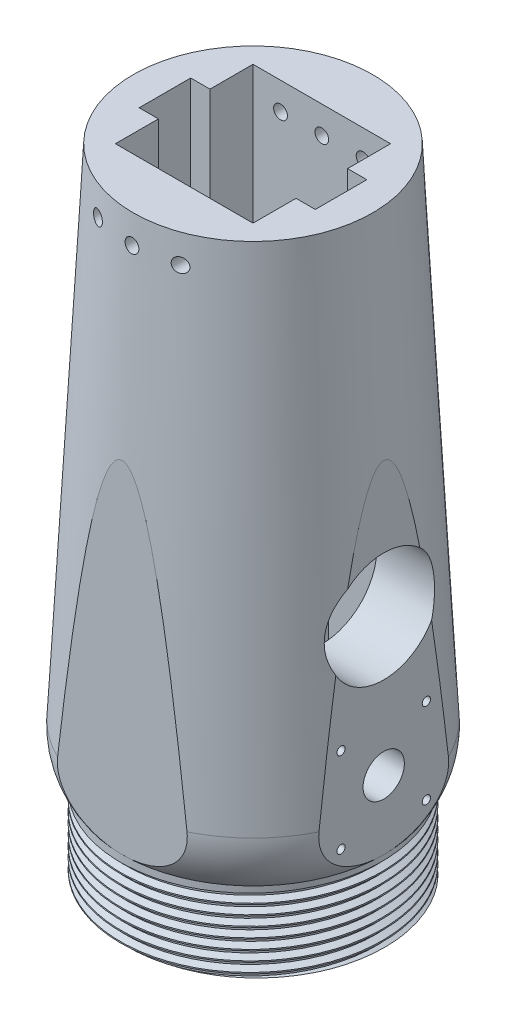
SolidWorks part; units mm, degrees
ref_plane "Front Plane" through (0, 0, 0) normal (0, 0, 1) x (1, 0, 0)
ref_plane "Top Plane" through (0, 0, 0) normal (0, 1, 0) x (1, 0, 0)
ref_plane "Right Plane" through (0, 0, 0) normal (1, 0, 0) x (0, 0, -1)
sketch "Sketch2" plane through (0, 0, 0) normal (0, 1, 0) x (1, 0, 0)
  circle A0 centre (0, 0) radius 47.5
  dimension "D1" = 95
extrude "Boss-Extrude1" add sketch "Sketch2" along normal blind 30
thread "Thread2" pitch 3.6286 method cut profile "Thread Profile2" start angle 0, offset 0, length 30, pitch 3.6286, diameter 95
ref_plane "Plane2" through (-47.5, 30, 0) normal (0, 0, 1) x (-1, 0, 0)
sketch "Thread Profile2" plane through (-47.5, 30, 0) normal (0, 0, 1) x (-1, 0, 0)
  line L0 (0, 0) -> (0, 3.6286) construction
  line L11 (0, 0) -> (0, 3.175)
  line L12 (0, 3.175) -> (-1.964, 2.0411)
  line L13 (-1.964, 2.0411) -> (-1.964, 1.1339)
  line L15 (-1.964, 1.1339) -> (0, 0)
  line L17 (-1.964, 1.5875) -> (0, 1.5875) construction
  point P2 (0, 0)
  dimension "Pitch" = 3.6286
  dimension "Profile_Angle" = 60
  dimension "Profile_Land" = 0.9071
  dimension "Profile_Height" = 1.964
sketch "Sketch12" plane through (0, 30, 0) normal (0, 1, 0) x (1, 0, 0)
  circle A0 centre (0, 0) radius 54
  dimension "D1" = 108
extrude "Boss-Extrude2" add sketch "Sketch12" along normal blind 200 draft 3
sketch "Sketch13" plane through (0, 230, 0) normal (0, 1, 0) x (1, 0, 0)
  line L1 (-25, 25) -> (25, 25)
  line L2 (-25, 25) -> (-25, -25)
  line L3 (-25, -25) -> (25, -25)
  line L4 (25, 25) -> (25, -25)
  line L5 (-25, 25) -> (25, -25) construction
  line L6 (-25, -25) -> (25, 25) construction
  point P0 (0, 0)
  dimension "D1" = 50
  dimension "D2" = 50
extrude "Cut-Extrude2" cut sketch "Sketch13" against normal up to surface (200 mm away) up to face at (0, 30, 54)
sketch "Sketch14" plane through (0, 230, 0) normal (0, 1, 0) x (1, 0, 0)
  line L5 (-47.5, 47.5) -> (47.5, 47.5)
  line L6 (-47.5, 47.5) -> (-47.5, -47.5)
  line L7 (-47.5, -47.5) -> (47.5, -47.5)
  line L8 (47.5, 47.5) -> (47.5, -47.5)
  line L9 (-47.5, 47.5) -> (47.5, -47.5) construction
  line L10 (-47.5, -47.5) -> (47.5, 47.5) construction
  circle A3 centre (0, 0) radius 67.1751
  point P0 (0, 0)
  point P1 (0, 0)
  dimension "D1" = 95
extrude "Cut-Extrude3" cut sketch "Sketch14" against normal up to surface (200 mm away) contours L6 A3 | L5 A3 | L8 A3 | L7 A3 region at (0, 230, -55.478) region at (-55.478, 230, 0) region at (55.478, 230, 0) region at (0, 230, 55.478) up to face at (0, 30, 54)
fillet "Fillet2" radius 30 4 edges at (-38.1838, 30, 38.1838) (-38.1838, 30, -38.1838) (38.1838, 30, 38.1838) (38.1838, 30, -38.1838)
sketch "Sketch15" plane through (-25, 0, 0) normal (1, 0, 0) x (0, 0, -1)
  line L1 (-21.15, 76.15) -> (21.15, 76.15)
  line L2 (-21.15, 76.15) -> (-21.15, 33.85)
  line L3 (-21.15, 33.85) -> (21.15, 33.85)
  line L4 (21.15, 76.15) -> (21.15, 33.85)
  line L5 (-21.15, 76.15) -> (21.15, 33.85) construction
  line L6 (-21.15, 33.85) -> (21.15, 76.15) construction
  point P0 (0, 55)
  dimension "D1" = 42.3
  dimension "D2" = 55
extrude "Cut-Extrude4" cut sketch "Sketch15" against normal up to next
sketch "Sketch16" plane through (0, 0, 25) normal (0, 0, -1) x (-1, 0, 0)
  line L1 (-2.5, 76) -> (2.5, 76)
  line L2 (-2.5, 76) -> (-2.5, 34)
  line L3 (-2.5, 34) -> (2.5, 34)
  line L4 (2.5, 76) -> (2.5, 34)
  line L5 (-2.5, 76) -> (2.5, 34) construction
  line L6 (-2.5, 34) -> (2.5, 76) construction
  point P0 (0, 55)
  dimension "D1" = 42
  dimension "D2" = 55
  dimension "D3" = 5
extrude "Boss-Extrude3" add sketch "Sketch16" along normal up to next
sketch "Sketch17" plane through (2.5, 0, 0) normal (1, 0, 0) x (0, 0, -1)
  line L1 (-15.5, 70.5) -> (15.5, 70.5)
  line L2 (-15.5, 70.5) -> (-15.5, 39.5)
  line L3 (-15.5, 39.5) -> (15.5, 39.5)
  line L4 (15.5, 70.5) -> (15.5, 39.5)
  line L5 (-15.5, 70.5) -> (15.5, 39.5) construction
  line L6 (-15.5, 39.5) -> (15.5, 70.5) construction
  circle A0 centre (-15.5, 70.5) radius 1.5
  circle A1 centre (15.5, 70.5) radius 1.5
  circle A2 centre (-15.5, 39.5) radius 1.5
  circle A3 centre (15.5, 39.5) radius 1.5
  circle A4 centre (0, 55) radius 7.5
  point P0 (0, 55)
  dimension "D3" = 3
  dimension "D4" = 15
  dimension "D1" = 31
  dimension "D2" = 31
  dimension "55" = 55
extrude "Cut-Extrude5" cut sketch "Sketch17" against normal through all both and the other way through all contours A0 | A4 | A1 | A2 | A3
sketch "Sketch18" plane through (0, 230, 0) normal (0, 1, 0) x (1, 0, 0)
  circle A0 centre (0, 0) radius 43.5184
  dimension "D1" = 87.0369
sketch "Sketch19" plane through (47.5, 0, 0) normal (1, 0, 0) x (0, 0, -1)
  circle A0 centre (0, 105) radius 20
  circle A1 centre (0, 55) radius 7.5 construction
  dimension "D1" = 40
  dimension "D2" = 50
extrude "Cut-Extrude6" cut sketch "Sketch19" against normal through all both and the other way through all
sketch "Sketch20" plane through (-25, 0, 0) normal (1, 0, 0) x (0, 0, -1)
  line L0 (25, 230) -> (-25, 230) construction
  line L1 (6.366, 105) -> (9.366, 105)
  line L2 (6.366, 105) -> (6.366, 230)
  line L3 (6.366, 230) -> (9.366, 230)
  line L4 (9.366, 105) -> (9.366, 230)
  line L6 (-6.366, 105) -> (-9.366, 105)
  line L7 (-6.366, 105) -> (-6.366, 230)
  line L8 (-6.366, 230) -> (-9.366, 230)
  line L9 (-9.366, 105) -> (-9.366, 230)
  circle A0 centre (0, 105) radius 6.366
  circle A1 centre (0, 105) radius 20 construction
  circle M3 centre (0, 105) radius 20
  line M10 (25, 230) -> (-25, 230)
  dimension "D1" = 12.732
  dimension "D2" = 3
  dimension "D3" = 3
extrude "Cut-Extrude7" cut sketch "Sketch20" against normal blind 7 and the other way blind 57 contours L9 L7 M3 M10 | L4 L2 M3 M10 region at (-25, 176.6814, -7.869) region at (-25, 176.6814, 7.869)
sketch "Sketch21" plane through (0, 230, 0) normal (0, 1, 0) x (1, 0, 0)
  line L1 (-32, 9.366) -> (-25, 9.366)
  line L2 (-32, 9.366) -> (-32, -9.366)
  line L3 (-32, -9.366) -> (-25, -9.366)
  line L4 (-25, 9.366) -> (-25, -9.366)
  line L5 (32, 9.366) -> (25, 9.366)
  line L6 (32, 9.366) -> (32, -9.366)
  line L7 (32, -9.366) -> (25, -9.366)
  line L8 (25, 9.366) -> (25, -9.366)
extrude "Cut-Extrude8" cut sketch "Sketch21" against normal up to surface (107.3286 mm away) up to face at (46.6662, 106.5841, 0.0383)
sketch "Sketch22" plane through (0, 230, 0) normal (0, 1, 0) x (1, 0, 0)
  line L1 (-25, 25) -> (25, 25)
  line L2 (-25, 25) -> (-25, -25)
  line L3 (-25, -25) -> (25, -25)
  line L4 (25, 25) -> (25, -25)
sketch "Sketch23" plane through (0, 0, 25) normal (0, 0, -1) x (-1, 0, 0)
  line L0 (25, 230) -> (-25, 230) construction
  circle A0 centre (0, 220) radius 2.5
  circle A1 centre (15, 220) radius 2.5
  circle A2 centre (-15, 220) radius 2.5
  point P9 (0, 230)
  dimension "D1" = 5
  dimension "D2" = 15
  dimension "D3" = 15
  dimension "D4" = 10
extrude "Cut-Extrude9" cut sketch "Sketch23" against normal through all both and the other way through all
